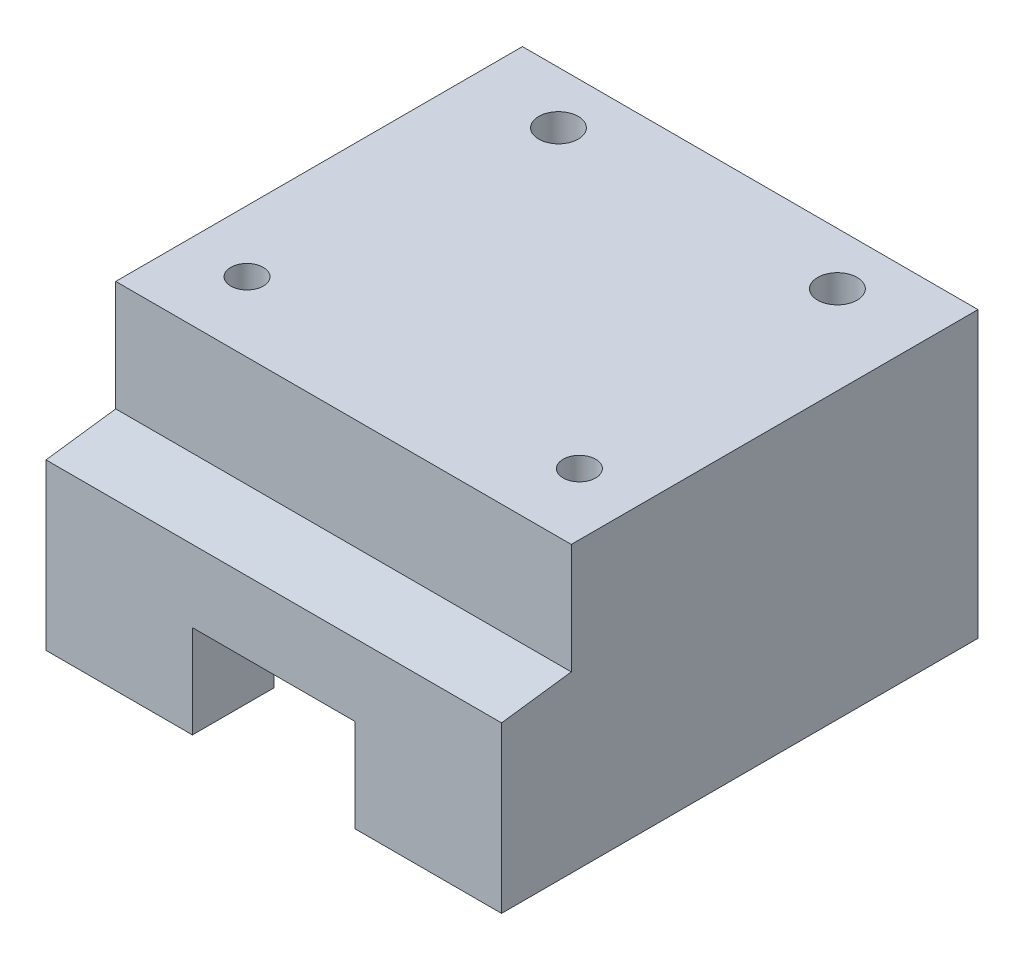
SolidWorks part; units mm, degrees
ref_plane "Спереди" through (0, 0, 0) normal (0, 0, 1) x (1, 0, 0)
ref_plane "Сверху" through (0, 0, 0) normal (0, 1, 0) x (1, 0, 0)
ref_plane "Справа" through (0, 0, 0) normal (1, 0, 0) x (0, 0, -1)
sketch "Эскиз1" plane through (0, 0, 0) normal (0, 0, 1) x (1, 0, 0)
  line L1 (20, -10) -> (-20, -10)
  line L2 (20, -10) -> (20, 10)
  line L3 (20, 10) -> (-20, 10)
  line L4 (-20, -10) -> (-20, 10)
  line L5 (20, -10) -> (-20, 10) construction
  line L6 (20, 10) -> (-20, -10) construction
  point P0 (0, 0)
  dimension "D1" = 40
  dimension "D2" = 20
extrude "Бобышка-Вытянуть1" add sketch "Эскиз1" along normal blind 6
sketch "Эскиз2" plane through (0, 0, 0) normal (0, 0, -1) x (-1, 0, 0)
  line L0 (20, -10) -> (-20, -10) construction
  line L1 (20, 22.5) -> (-20, 22.5)
  line L2 (20, 22.5) -> (20, -10)
  line L3 (20, -10) -> (-20, -10)
  line L4 (-20, 22.5) -> (-20, -10)
  line L5 (20, 22.5) -> (-20, -10) construction
  line L6 (20, -10) -> (-20, 22.5) construction
  line L7 (-20, -10) -> (-20, 10) construction
  point P0 (0, 6.25)
  dimension "D1" = 22.5
extrude "Бобышка-Вытянуть2" add sketch "Эскиз2" along normal blind 35
sketch "Эскиз3" plane through (0, -10, 0) normal (0, -1, 0) x (1, 0, 0)
  line L0 (0, 6) -> (0, -35) construction
  line L1 (-20, 6) -> (20, 6) construction
  line L2 (20, -35) -> (-20, -35) construction
  line L3 (-7, 6) -> (-7, -1)
  line L4 (-7, -1) -> (-8.6, -1)
  line L5 (-8.6, -1) -> (-8.6, -18.5)
  line L6 (-8.6, -18.5) -> (-4.5, -30.5)
  line L7 (-4.5, -30.5) -> (-4.5, -34)
  line L8 (-4.5, -34) -> (-3.5, -34)
  line L9 (-3.5, -34) -> (-3.5, -35)
  line L10 (3.5, -34) -> (3.5, -35)
  line L11 (4.5, -34) -> (3.5, -34)
  line L12 (4.5, -30.5) -> (4.5, -34)
  line L13 (8.6, -18.5) -> (4.5, -30.5)
  line L14 (8.6, -1) -> (8.6, -18.5)
  line L15 (7, -1) -> (8.6, -1)
  line L16 (7, 6) -> (7, -1)
  line L17 (-7, 6) -> (7, 6)
  line L18 (3.5, -35) -> (-3.5, -35)
  dimension "D1" = 7
  dimension "D2" = 8.6
  dimension "D3" = 4.5
  dimension "D4" = 3.5
  dimension "D5" = 7
  dimension "D6" = 17.5
  dimension "D7" = 33
  dimension "D8" = 29.5
extrude "Вырез-Вытянуть1" cut sketch "Эскиз3" against normal blind 13
sketch "Эскиз5" plane through (0, 3, 0) normal (0, -1, 0) x (1, 0, 0)
  line L0 (-8.6, -1) -> (8.6, -1)
  line L1 (8.6, -1) -> (8.6, -18.5)
  line L2 (8.6, -18.5) -> (4.5, -30.5)
  line L3 (4.5, -30.5) -> (4.5, -34)
  line L4 (4.5, -34) -> (-4.5, -34)
  line L5 (-4.5, -34) -> (-4.5, -30.5)
  line L6 (-4.5, -30.5) -> (-8.6, -18.5)
  line L7 (-8.6, -18.5) -> (-8.6, -1)
extrude "Вырез-Вытянуть2" cut sketch "Эскиз5" against normal blind 2
sketch "Эскиз6" plane through (0, -10, 0) normal (0, -1, 0) x (1, 0, 0)
  line L0 (20, 6) -> (20, -35) construction
  line L1 (-20, -35) -> (20, -35)
  line L2 (-20, -35) -> (-20, 6)
  line L3 (-20, 6) -> (20, 6)
  line L4 (20, -35) -> (20, 6)
  line L6 (-20, 6) -> (-7, 6) construction
extrude "Вырез-Вытянуть3" cut sketch "Эскиз6" against normal blind 5
sketch "Эскиз8" plane through (0, -5, 0) normal (0, -1, 0) x (1, 0, 0)
  line L0 (0, 6) -> (0, -35) construction
  line L1 (7, 6) -> (-7, 6) construction
  line L2 (-3.5, -35) -> (3.5, -35) construction
  line L3 (8.6, -6) -> (20, -6) construction
  line L4 (8.6, -18.5) -> (8.6, -1) construction
  line L5 (20, -35) -> (20, 6) construction
  line L6 (20, 6) -> (7, 6) construction
  circle A0 centre (12, -30.5) radius 1.7
  circle A1 centre (14.3, -6) radius 1.4
  circle A2 centre (-12, -30.5) radius 1.7
  circle A3 centre (-14.3, -6) radius 1.4
  dimension "D1" = 12
  dimension "D2" = 3.4
  dimension "D4" = 2.8
  dimension "D3" = 12
extrude "Вырез-Вытянуть4" cut sketch "Эскиз8" against normal through all
sketch "Эскиз9" plane through (0, 0, 0) normal (0, 0, 1) x (1, 0, 0)
  line L2 (20, 22.5) -> (20, 10) construction
  line L3 (-20, 22.5) -> (20, 22.5)
  line L4 (-20, 22.5) -> (-20, 19.5)
  line L5 (-20, 19.5) -> (20, 19.5)
  line L6 (20, 22.5) -> (20, 19.5)
  dimension "D1" = 3
extrude "Вырез-Вытянуть5" cut sketch "Эскиз9" against normal up to surface (35 mm away) up to face at (0, 3.875, -35)
chamfer "Фаска1" distance 6 distance2 0.8 1 edges at (0, 10, 6) first distance on face at (0, 10, 3)
sketch "Эскиз11" plane through (0, 19.5, 0) normal (0, 1, 0) x (1, 0, 0)
  line L0 (20, 35) -> (-20, 35) construction
  line L1 (-19.6, 35) -> (-20, 35)
  line L2 (-19.6, 35) -> (-19.6, -6)
  line L3 (-19.6, -6) -> (-20, -6)
  line L4 (-20, 35) -> (-20, -6)
  line L5 (20, -6) -> (-20, -6) construction
  line L6 (-20, 35) -> (-20, 0) construction
  line L7 (0, 35) -> (0, -6) construction
  line L8 (20, 35) -> (20, -6)
  line L9 (19.6, -6) -> (20, -6)
  line L10 (19.6, 35) -> (19.6, -6)
  line L11 (19.6, 35) -> (20, 35)
  dimension "D1" = 0.4
extrude "Вырез-Вытянуть6" cut sketch "Эскиз11" against normal up to surface (24.5 mm away) up to face at (15.7, -5, -6)
